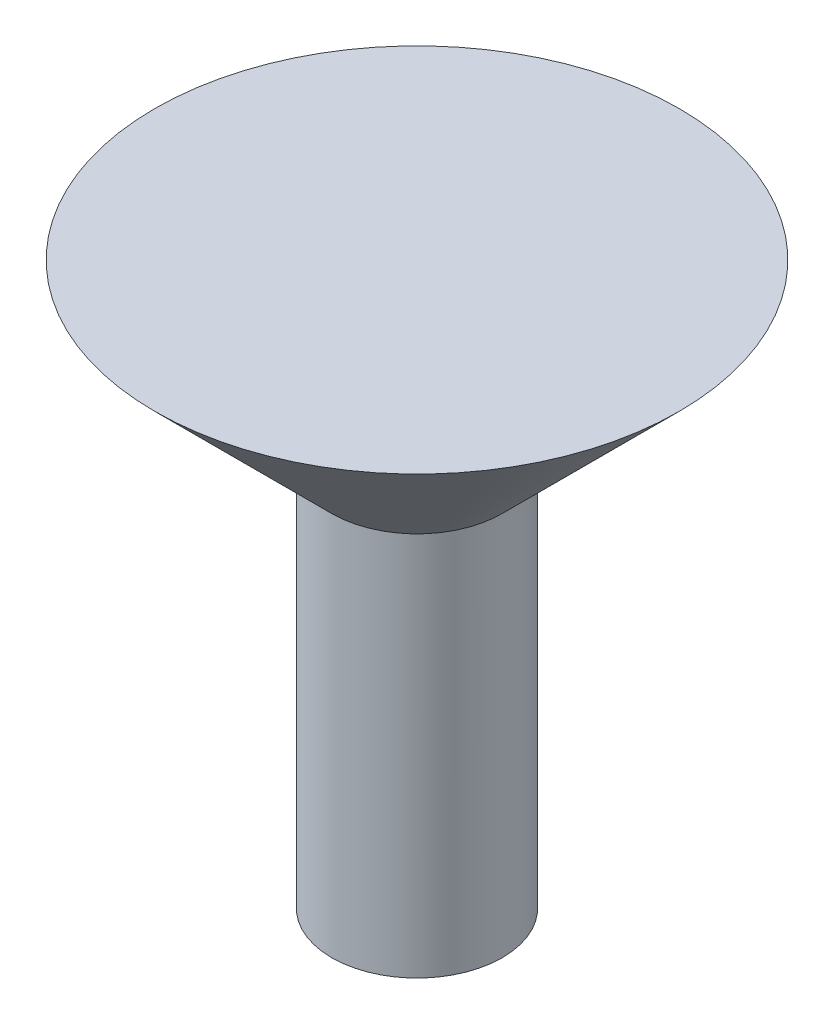
SolidWorks part; units mm, degrees
ref_plane "Front Plane" through (0, 0, 0) normal (0, 0, 1) x (1, 0, 0)
ref_plane "Top Plane" through (0, 0, 0) normal (0, 1, 0) x (1, 0, 0)
ref_plane "Right Plane" through (0, 0, 0) normal (1, 0, 0) x (0, 0, -1)
sketch "Sketch1" plane through (0, 0, 0) normal (0, 0, 1) x (1, 0, 0)
  line L0 (0, 2.5) -> (0, -2.5) construction
  line L1 (0, -2.5) -> (-2.5, -2.5) construction
  line L2 (-2.5, -2.5) -> (-7.5, 2.5) construction
  line L3 (-7.5, 2.5) -> (0, 2.5) construction
  line L4 (-0.2, 2.3) -> (-0.2, -2.3)
  line L5 (-0.2, -2.3) -> (-2.4172, -2.3)
  line L6 (-2.4172, -2.3) -> (-7.0172, 2.3)
  line L7 (-7.0172, 2.3) -> (-0.2, 2.3)
  dimension "D1" = 5
  dimension "D2" = 7.5
  dimension "D3" = 2.5
  dimension "D4" = 0.2
revolve "Revolve1" add sketch "Sketch1" angle 360 about L4
sketch "Sketch2" plane through (0, -2.3, 0) normal (0, -1, 0) x (1, 0, 0)
  circle A1 centre (-0.2, 0) radius 2.2172
  circle A2 centre (-0.2, 0) radius 2.2172
  dimension "D1" = 0
extrude "Boss-Extrude1" add sketch "Sketch2" along normal blind 10
sketch "Sketch3" plane through (0, -12.3, 0) normal (0, -1, 0) x (1, 0, 0)
  circle A0 centre (-0.2, 0) radius 1.5
  circle A1 centre (-0.2, 0) radius 2.2172 construction
  dimension "D1" = 3
extrude "Boss-Extrude2" add sketch "Sketch3" against normal blind 3
extrude "Cut-Extrude1" cut sketch "Sketch3<2>" against normal blind 5
sketch "Sketch3<2>" plane through (0, -12.3, 0) normal (0, -1, 0) x (1, 0, 0) same geometry as "Sketch3"
